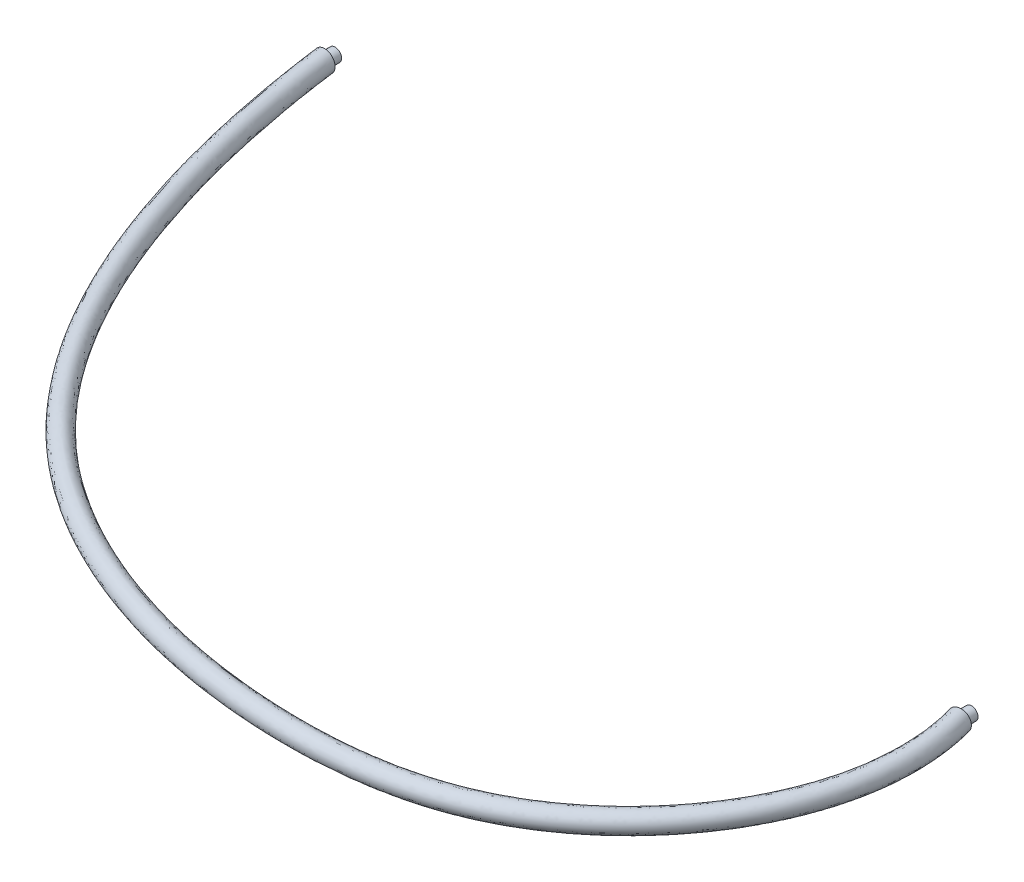
SolidWorks part; units mm, degrees
ref_plane "Alzado" through (0, 0, 0) normal (0, 0, 1) x (1, 0, 0)
ref_plane "Planta" through (0, 0, 0) normal (0, 1, 0) x (1, 0, 0)
ref_plane "Vista lateral" through (0, 0, 0) normal (1, 0, 0) x (0, 0, -1)
sketch "Guia Riel" plane through (0, 0, 0) normal (0, 1, 0) x (1, 0, 0)
  line L0 (-30.1885, -55.3854) -> (152.8112, -55.3854) construction
  spline S0 degree 3 poles (0, 0) (4.0736, -31.1207) (22.459, -93.9292) (93.6908, -117.6683) (153.4091, -109.8396) (176.5257, -72.3519) (170, -48.5139) knots 0 0 0 0 0.362124 0.618239 0.744006 1 1 1 1
  point P4 (0, 0)
  point P6 (0, 0)
  point P8 (168.7538, -75.2672)
  point P10 (0, 0)
  point P12 (139.847, -107.8779)
  point P14 (39.6112, -89.918)
  point P15 (0, 0)
  dimension "D1" = 50
  dimension "D2" = 30
  dimension "D3" = 170
sketch "Circulo Barrido" plane through (0, 0, 0) normal (0, 0, 1) x (1, 0, 0)
  circle A0 centre (0, 0) radius 2
  dimension "D1" = 4
sweep "Barrido Riel" add profiles "Circulo Barrido" path "Guia Riel"
sketch "Croquis3" plane through (0, 0, 0) normal (0, 0, 1) x (1, 0, 0)
  circle A0 centre (0, 0) radius 1.25
  point P5 (0, 0)
  point P7 (160.6289, 7.3444)
  dimension "D2" = 2.5
extrude "Encastre 1" add sketch "Croquis3" against normal blind 2
sketch "Croquis4" plane through (0, 0, 0) normal (0, 0, 1) x (1, 0, 0)
  circle A0 centre (170, 0) radius 1.25
  ellipse E0 centre (170, 0) end of major axis (170, 2) minor radius 1.9812 construction
  dimension "D1" = 2.5
extrude "Encastre 2 Saliente" add sketch "Croquis4" along normal up to next
sketch "Croquis5" plane through (0, 0, 0) normal (0, 1, 0) x (1, 0, 0)
  line L0 (171.25, 0) -> (168.75, 0) construction
  line L1 (168.75, 0) -> (171.25, 0)
  line L2 (168.75, 0) -> (168.75, -46.2406)
  line L3 (168.75, -46.2406) -> (171.25, -46.2406)
  line L4 (171.25, 0) -> (171.25, -46.2406)
  line L5 (168.75, 0) -> (168.75, -48.6863) construction
  line L6 (171.25, -48.3415) -> (171.25, 0) construction
  dimension "D1" = 2
extrude "Encastre 2 Corte" cut sketch "Croquis5" against normal up to next and the other way up to next
